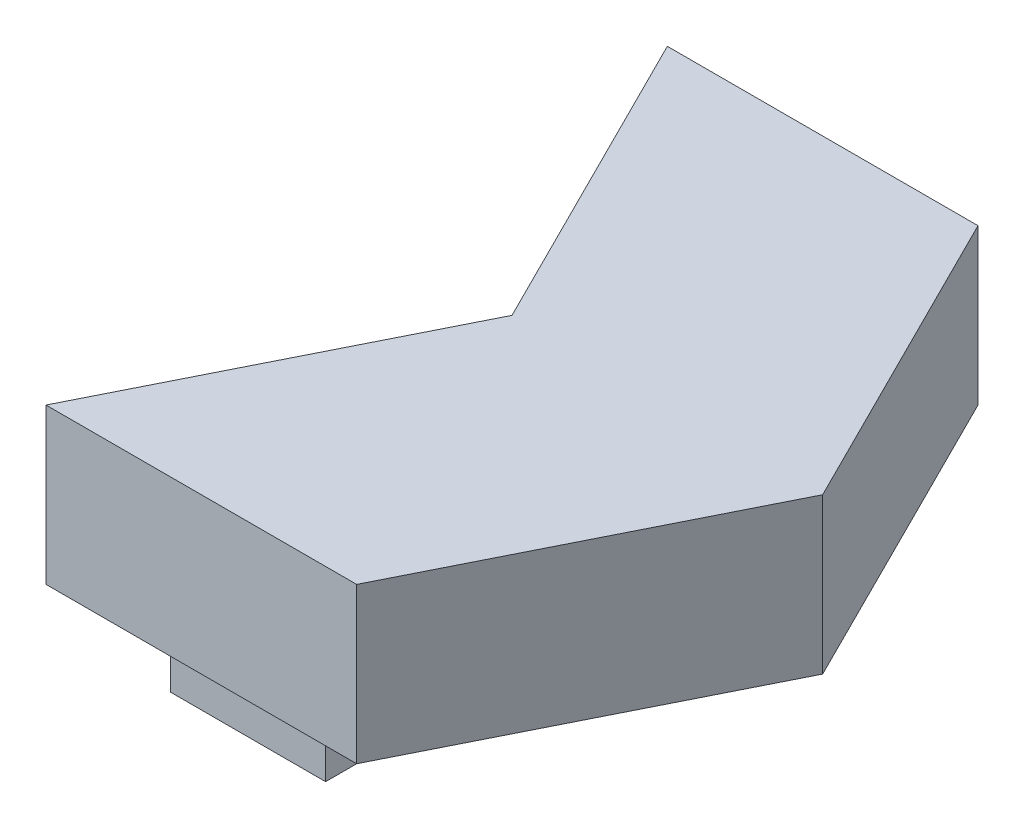
SolidWorks part; units mm, degrees
ref_plane "Front Plane" through (0, 0, 0) normal (0, 0, 1) x (1, 0, 0)
ref_plane "Top Plane" through (0, 0, 0) normal (0, 1, 0) x (1, 0, 0)
ref_plane "Right Plane" through (0, 0, 0) normal (1, 0, 0) x (0, 0, -1)
sketch "Sketch1" plane through (0, 0, 0) normal (0, 1, 0) x (1, 0, 0)
  line L0 (0, 0) -> (12.7, 0)
  line L1 (12.7, 0) -> (19.05, 12.7)
  line L2 (19.05, 12.7) -> (12.7, 25.4)
  line L3 (12.7, 25.4) -> (0, 25.4)
  line L4 (0, 25.4) -> (6.35, 12.7)
  line L5 (6.35, 12.7) -> (0, 0)
  point P5 (0, 0)
  point P8 (0, 0)
  point P9 (0, 0)
  point P10 (0, 0)
  point P11 (0, 0)
  dimension "D1" = 12.7
  dimension "D2" = 25.4
  dimension "D3" = 6.35
  dimension "D5" = 12.7
extrude "Boss-Extrude1" add sketch "Sketch1" along normal blind 6.35
sketch "Sketch2" plane through (0, 0, 0) normal (0, -1, 0) x (1, 0, 0)
  line L0 (19.05, -12.7) -> (6.35, -12.7) construction
  line L1 (6.35, -12.7) -> (0, 0) construction
  circle A0 centre (12.192, -12.7) radius 5.127
  point P7 (0, 0)
  point P8 (0, 0)
  point P9 (0, 0)
  point P10 (0, 0)
  dimension "D1" = 10.254
  dimension "D2" = 5.842
extrude "Cut-Extrude1" cut sketch "Sketch2" against normal blind 2.7 contours A0
sketch "Sketch3" plane through (0, 0, 0) normal (0, -1, 0) x (1, 0, 0)
  line L8 (11.1065, -17.7108) -> (8.8347, -16.5749)
  line L9 (11.1065, -17.7108) -> (9.4026, -21.1185)
  line L10 (8.8347, -16.5749) -> (7.1308, -19.9826)
  line L11 (9.4026, -21.1185) -> (7.1308, -19.9826)
  line L12 (19.05, -12.7) -> (12.7, -25.4) construction
  circle A3 centre (12.192, -12.7) radius 5.127 construction
  dimension "D1" = 2.54
  dimension "D2" = 3.81
extrude "Cut-Extrude2" cut sketch "Sketch3" against normal blind 2.7
ref_plane "MidPlane" through (0, 0, -12.7) normal (0, 0, -1) x (-1, 0, 0)
sketch "Sketch4" plane through (0, 0, 0) normal (0, -1, 0) x (1, 0, 0)
  line L0 (12.7, -25.4) -> (0, -25.4) construction
  line L1 (10.16, -24.13) -> (3.81, -24.13)
  line L2 (10.16, -24.13) -> (10.16, -21.59)
  line L3 (10.16, -21.59) -> (3.81, -21.59)
  line L4 (3.81, -24.13) -> (3.81, -21.59)
  line L5 (0, -3.4925) -> (0, 3.4925) construction
  dimension "D1" = 2.54
  dimension "D2" = 6.35
  dimension "D3" = 1.27
  dimension "D4" = 3.81
extrude "Boss-Extrude2" add sketch "Sketch4" along normal blind 2.54
mirror "Mirror1" about plane through (0, 0, -12.7) normal (0, 0, -1) of "Boss-Extrude2"
equation "\"Arrow Height\"= 1in"
equation "\"Button Height\"= 2in"
equation "\"Button Width\"= 4in"
equation "\"Haptic Diameter\"= 10mm"
equation "\"Haptic Thickness\"= 2.7mm"
equation "\"D2@Sketch1\"=\"Arrow Height\""
equation "\"D5@Sketch1\"=\"Arrow Height\"/2"
equation "\"D1@Sketch2\"=\"Haptic Diameter\" + .01in"
equation "\"D1@Cut-Extrude1\"=\"Haptic Thickness\""
equation "\"D1@Cut-Extrude2\"=\"Haptic Thickness\""
